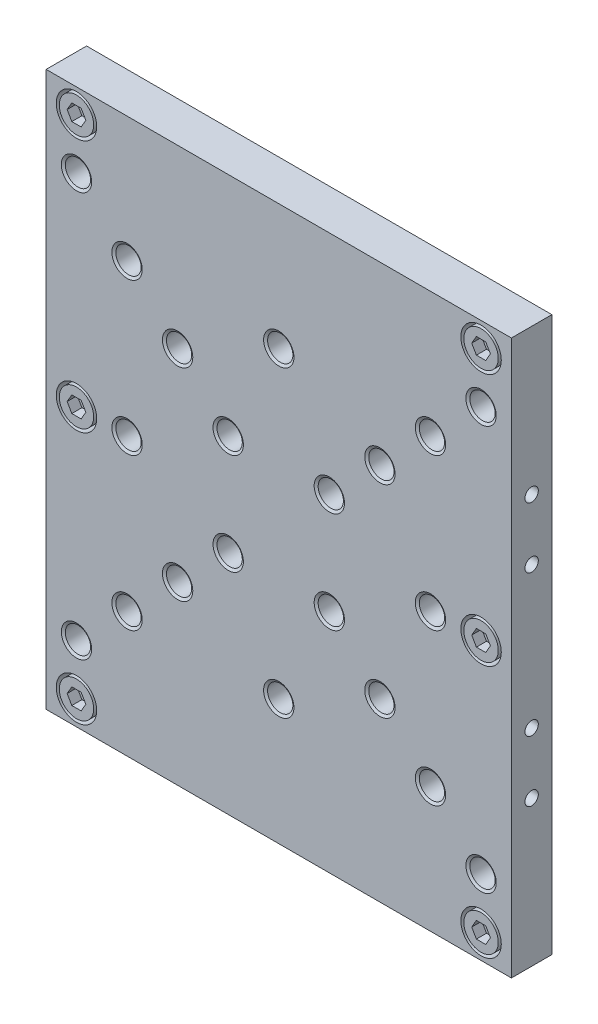
SolidWorks part; units mm, degrees
note: '?' marks a value the reader was unsure of.
material "Aluminum Black Anodize"
ref_plane "Front" through (0, 0, 0) normal (0, 0, 1) x (1, 0, 0)
ref_plane "Top" through (0, 0, 0) normal (0, 1, 0) x (1, 0, 0)
ref_plane "Right" through (0, 0, 0) normal (1, 0, 0) x (0, 0, -1)
ref_axis "Axis1" through (0, 0, -0.5) along (0, 0, 1)?
sketch "Sketch1" plane through (0, 0, 0) normal (0, 0, 1) x (1, 0, 0)
  line L1 (57.5, -68.5) -> (-57.5, -68.5)
  line L2 (57.5, -68.5) -> (57.5, 68.5)
  line L3 (57.5, 68.5) -> (-57.5, 68.5)
  line L4 (-57.5, -68.5) -> (-57.5, 68.5)
  point P4 (57.5, 0)
  point P5 (0, 68.5)
  dimension "D1" = 115
  dimension "D2" = 137
extrude "Extrude1" add sketch "Sketch1" along normal blind 10
hole_wizard "CBORE for M5 SHCS1" positions "Sketch7" profile "Sketch6" counterbore size "M5" standard "ANSI Metric" end condition through all
sketch "Sketch7" plane through (0, 0, 10) normal (0, 0, 1) x (1, 0, 0)
  line L5 (-57.5, 0) -> (57.5, 0) construction
  line L6 (-57.5, 68.5) -> (-57.5, -68.5) construction
  line L7 (57.5, -68.5) -> (57.5, 68.5) construction
  line L8 (0, -68.5) -> (0, 68.5) construction
  line L9 (-57.5, -68.5) -> (57.5, -68.5) construction
  line L10 (57.5, 68.5) -> (-57.5, 68.5) construction
  point P13 (50, 62.5)
  point P15 (50, 0)
  point P48 (-50, 0)
  point P49 (-50, 62.5)
  point P56 (-50, -62.5)
  point P59 (50, -62.5)
  dimension "D1" = 125
  dimension "D9" = 50
sketch "Sketch6" plane through (50, 62.5, 10) normal (1, 0, 0) x (0, -1, 0)
  line L0 (0, 0) -> (0, 10)
  line L1 (0, 10) -> (2.8956, 10)
  line L3 (2.8956, 10) -> (2.8956, 5.5)
  line L4 (2.8956, 5.5) -> (5, 5.5)
  line L5 (5, 5.5) -> (5, 0)
  line L7 (5, 0) -> (0, 0)
  line L11 (0, -6.35) -> (0, 107.95) construction
  dimension "Thru Hole Dia." = 5.7912
  dimension "Thru Hole Depth" = 10
  dimension "C'Bore Dia." = 10
  dimension "C'Bore Depth" = 5.5
hole_wizard "Tapped Hole for M6x1.0 Helicoil1" positions "Sketch3" profile "Sketch2" tap size "M6x1.0" standard "Helicoil® Metric" end condition through all
sketch "Sketch3" plane through (0, 0, 10) normal (0, 0, 1) x (1, 0, 0)
  line L0 (0, 0) -> (-141.3203, 0) construction
  line L1 (0, 0) -> (0, 79.9717) construction
  line L2 (-57.5, -68.5) -> (57.5, -68.5) construction
  point P0 (12.5, 12.5)
  point P1 (-12.5, 12.5)
  point P2 (12.5, -12.5)
  point P7 (-12.5, -12.5)
  point P8 (25, 25)
  point P9 (25, -25)
  point P10 (-25, -25)
  point P11 (-25, 25)
  point P12 (37.5, 37.5)
  point P13 (37.5, -37.5)
  point P14 (-37.5, 37.5)
  point P15 (-37.5, -37.5)
  point P16 (37.5, 0)
  point P21 (-37.5, 0)
  point P22 (0, 37.5)
  point P23 (0, -37.5)
  dimension "D1" = 12.5
  dimension "D2" = 12.5
  dimension "D3" = 25
  dimension "D4" = 25
  dimension "D5" = 37.5
  dimension "D6" = 37.5
cosmetic thread "Hole Thread5" parameters "D1"=7, "D2"=7.422
cosmetic thread "Hole Thread6" parameters "D1"=7, "D2"=7.422
cosmetic thread "Hole Thread7" parameters "D1"=7, "D2"=7.422
cosmetic thread "Hole Thread8" parameters "D1"=7, "D2"=7.422
cosmetic thread "Hole Thread9" parameters "D1"=7, "D2"=7.422
cosmetic thread "Hole Thread10" parameters "D1"=7, "D2"=7.422
cosmetic thread "Hole Thread11" parameters "D1"=7, "D2"=7.422
cosmetic thread "Hole Thread12" parameters "D1"=7, "D2"=7.422
cosmetic thread "Hole Thread13" parameters "D1"=7, "D2"=7.422
cosmetic thread "Hole Thread14" parameters "D1"=7, "D2"=7.422
cosmetic thread "Hole Thread15" parameters "D1"=7, "D2"=7.422
cosmetic thread "Hole Thread16" parameters "D1"=7, "D2"=7.422
cosmetic thread "Hole Thread17" parameters "D1"=7, "D2"=7.422
cosmetic thread "Hole Thread18" parameters "D1"=7, "D2"=7.422
cosmetic thread "Hole Thread19" parameters "D1"=7, "D2"=7.422
cosmetic thread "Hole Thread20" parameters "D1"=7, "D2"=7.422
sketch "Sketch2" plane through (12.5, 12.5, 10) normal (1, 0, 0) x (0, -1, 0)
  line L0 (0, 0) -> (0, 10)
  line L1 (0, 10) -> (3.125, 10)
  line L2 (3.125, 10) -> (3.125, 0.3608)
  line L3 (3.125, 0.3608) -> (3.75, 0)
  line L5 (3.75, 0) -> (0, 0)
  line L6 (-3.125, 0.3608) -> (-3.75, 0) construction
  line L11 (0, -6.35) -> (0, 107.95) construction
  dimension "Thru Tap Drill Dia." = 6.25
  dimension "Thru Tap Drill Depth" = 10
  dimension "Near C'Sink Dia." = 7.5
  dimension "Near C'Sink Angle" = 120
hole_wizard "Tapped Hole for M6x1.0 Helicoil2" positions "Sketch11" profile "Sketch10" tap size "M6x1.0" standard "Helicoil® Metric" end condition through all
sketch "Sketch11" plane through (0, 0, 10) normal (0, 0, 1) x (1, 0, 0)
  line L4 (-50, 50) -> (50, 50) construction
  line L5 (50, 50) -> (50, -50) construction
  line L6 (50, -50) -> (-50, -50) construction
  line L7 (-50, -50) -> (-50, 50) construction
  line L8 (-50, 50) -> (50, -50) construction
  point P0 (-50, 50)
  point P1 (50, 50)
  point P3 (50, -50)
  point P5 (-50, -50)
  dimension "D1" = 100
  dimension "D2" = 100
cosmetic thread "Hole Thread37" parameters "D1"=7, "D2"=7.422
cosmetic thread "Hole Thread38" parameters "D1"=7, "D2"=7.422
cosmetic thread "Hole Thread39" parameters "D1"=7, "D2"=7.422
cosmetic thread "Hole Thread40" parameters "D1"=7, "D2"=7.422
sketch "Sketch10" plane through (-50, 50, 10) normal (1, 0, 0) x (0, -1, 0)
  line L0 (0, 0) -> (0, 10)
  line L1 (0, 10) -> (3.125, 10)
  line L2 (3.125, 10) -> (3.125, 0.3608)
  line L3 (3.125, 0.3608) -> (3.75, 0)
  line L5 (3.75, 0) -> (0, 0)
  line L6 (-3.125, 0.3608) -> (-3.75, 0) construction
  line L11 (0, -6.35) -> (0, 107.95) construction
  dimension "Thru Tap Drill Dia." = 6.25
  dimension "Thru Tap Drill Depth" = 10
  dimension "Near C'Sink Dia." = 7.5
  dimension "Near C'Sink Angle" = 120
hole_wizard "Tapped Hole for 1/4-20 Helicoil1" [suppressed] positions "Sketch9" profile "Sketch8" tap size "1/4-20" standard "Helicoil® Inch"
sketch "Sketch9" [suppressed] plane through (0, 0, 10) normal (0, 0, 1) x (1, 0, 0)
  line L0 (-62.9542, 0) -> (64.4183, 0) construction
  line L1 (0, 59.6195) -> (0, -44.1656) construction
  line L2 (0, 0) -> (69.2893, 69.2893) construction
  point P1 (-12.7, 12.7)
  point P2 (-12.7, -12.7)
  point P3 (12.7, -12.7)
  point P4 (12.7, 12.7)
  point P8 (-25.4, 25.4)
  point P10 (25.4, 25.4)
  point P11 (25.4, -25.4)
  point P12 (-25.4, -25.4)
  point P13 (-38.1, 38.1)
  point P14 (0, 38.1)
  point P15 (38.1, 38.1)
  point P16 (38.1, 0)
  point P17 (38.1, -38.1)
  point P18 (0, -38.1)
  point P19 (-38.1, -38.1)
  point P20 (-38.1, 0)
  point P27 (50.8, 50.8)
  point P30 (-50.8, 50.8)
  point P31 (-50.8, -50.8)
  point P32 (50.8, -50.8)
  dimension "D1" = 12.7
  dimension "D2" = 45
  dimension "D3" = 25.4
  dimension "D4" = 50.8
  dimension "D5" = 38.1
cosmetic thread "Hole Thread21" [suppressed] parameters "D1"=7.62, "D2"=8.095
cosmetic thread "Hole Thread22" [suppressed] parameters "D1"=7.62, "D2"=8.095
cosmetic thread "Hole Thread23" [suppressed] parameters "D1"=7.62, "D2"=8.095
cosmetic thread "Hole Thread24" [suppressed] parameters "D1"=7.62, "D2"=8.095
cosmetic thread "Hole Thread25" [suppressed] parameters "D1"=7.62, "D2"=8.095
cosmetic thread "Hole Thread26" [suppressed] parameters "D1"=7.62, "D2"=8.095
cosmetic thread "Hole Thread27" [suppressed] parameters "D1"=7.62, "D2"=8.095
cosmetic thread "Hole Thread28" [suppressed] parameters "D1"=7.62, "D2"=8.095
cosmetic thread "Hole Thread29" [suppressed] parameters "D1"=7.62, "D2"=8.095
cosmetic thread "Hole Thread30" [suppressed] parameters "D1"=7.62, "D2"=8.095
cosmetic thread "Hole Thread31" [suppressed] parameters "D1"=7.62, "D2"=8.095
cosmetic thread "Hole Thread32" [suppressed] parameters "D1"=7.62, "D2"=8.095
cosmetic thread "Hole Thread33" [suppressed] parameters "D1"=7.62, "D2"=8.095
cosmetic thread "Hole Thread34" [suppressed] parameters "D1"=7.62, "D2"=8.095
cosmetic thread "Hole Thread35" [suppressed] parameters "D1"=7.62, "D2"=8.095
cosmetic thread "Hole Thread36" [suppressed] parameters "D1"=7.62, "D2"=8.095
cosmetic thread "Hole Thread55" [suppressed] parameters "D1"=7.62, "D2"=8.095
cosmetic thread "Hole Thread56" [suppressed] parameters "D1"=7.62, "D2"=8.095
cosmetic thread "Hole Thread57" [suppressed] parameters "D1"=7.62, "D2"=8.095
cosmetic thread "Hole Thread58" [suppressed] parameters "D1"=7.62, "D2"=8.095
sketch "Sketch8" [suppressed] plane through (-12.7, 12.7, 10) normal (1, 0, 0) x (0, -1, 0)
  line L0 (0, 0) -> (0, 10)
  line L1 (0, 10) -> (3.3782, 10)
  line L2 (3.3782, 10) -> (3.3782, 0.4326)
  line L3 (3.3782, 0.4326) -> (4.1275, 0)
  line L5 (4.1275, 0) -> (0, 0)
  line L6 (-3.3782, 0.4326) -> (-4.1275, 0) construction
  line L11 (0, -6.35) -> (0, 107.95) construction
  dimension "Thru Tap Drill Dia." = 6.7564
  dimension "Thru Tap Drill Depth" = 10
  dimension "Near C'Sink Dia." = 8.255
  dimension "Near C'Sink Angle" = 120
hole_wizard "M2.5x0.45 Tapped Hole1" [suppressed] positions "Sketch13" profile "Sketch12" tap size "M2.5x0.45" standard "ANSI Metric"
sketch "Sketch13" [suppressed] plane through (0, -68.5, 0) normal (0, -1, 0) x (1, 0, 0)
  line L4 (0, 0) -> (0, 10) construction
  line L5 (-57.5, 0) -> (57.5, 0) construction
  point P0 (0, 6)
  point P3 (35, 6)
  point P26 (-35, 6)
  dimension "D1" = 6
  dimension "D2" = 35
  dimension "D5" = 35
sketch "Sketch12" [suppressed] plane through (0, -68.5, 6) normal (1, 0, 0) x (0, 0, -1)
  line L0 (0, 0) -> (0, 7.8659)
  line L1 (0, 7.8659) -> (1.025, 7.25)
  line L2 (1.025, 7.25) -> (1.025, 0)
  line L5 (1.025, 0) -> (0, 0)
  line L10 (0, 7.8659) -> (-1.025, 7.25) construction
  line L11 (0, -6.35) -> (0, 107.95) construction
  dimension "Tap Drill Dia." = 2.05
  dimension "Tap Drill Depth" = 7.25
  dimension "Drill Angle" = 118
cosmetic thread "Hole Thread49" [suppressed] parameters "D1"=5, "D2"=2.5
cosmetic thread "Hole Thread50" [suppressed] parameters "D1"=5, "D2"=2.5
cosmetic thread "Hole Thread51" [suppressed] parameters "D1"=5, "D2"=2.5
hole_wizard "M2.5x0.45 Tapped Hole2" [suppressed] positions "Sketch15" profile "Sketch14" tap size "M2.5x0.45" standard "ANSI Metric"
sketch "Sketch15" [suppressed] plane through (0, 68.5, 0) normal (0, 1, 0) x (-1, 0, 0)
  point P5 (-35, 6)
  point P7 (0, 6)
  point P14 (35, 6)
sketch "Sketch14" [suppressed] plane through (35, 68.5, 6) normal (1, 0, 0) x (0, 0, 1)
  line L0 (0, 0) -> (0, 7.8659)
  line L1 (0, 7.8659) -> (1.025, 7.25)
  line L2 (1.025, 7.25) -> (1.025, 0)
  line L5 (1.025, 0) -> (0, 0)
  line L10 (0, 7.8659) -> (-1.025, 7.25) construction
  line L11 (0, -6.35) -> (0, 107.95) construction
  dimension "Tap Drill Dia." = 2.05
  dimension "Tap Drill Depth" = 7.25
  dimension "Drill Angle" = 118
cosmetic thread "Hole Thread52" [suppressed] parameters "D1"=5, "D2"=2.5
cosmetic thread "Hole Thread53" [suppressed] parameters "D1"=5, "D2"=2.5
cosmetic thread "Hole Thread54" [suppressed] parameters "D1"=5, "D2"=2.5
hole_wizard "CBORE for M5 SHCS2" [suppressed] positions "Sketch19" profile "Sketch18" counterbore size "M5" standard "Ansi Metric"
sketch "Sketch19" [suppressed] plane through (0, 0, 0) normal (0, 0, -1) x (-1, 0, 0)
  line L0 (37.5, 12.5) -> (37.5, -12.5) construction
  line L1 (37.5, -12.5) -> (-37.5, -12.5) construction
  line L2 (-37.5, -12.5) -> (-37.5, 12.5) construction
  line L3 (-37.5, 12.5) -> (37.5, 12.5) construction
  line L4 (37.5, 12.5) -> (-37.5, -12.5) construction
  line L5 (12.5, -37.5) -> (-12.5, -37.5) construction
  line L6 (-12.5, -37.5) -> (-12.5, 37.5) construction
  line L7 (-12.5, 37.5) -> (12.5, 37.5) construction
  line L8 (12.5, 37.5) -> (12.5, -37.5) construction
  line L9 (12.5, -37.5) -> (-12.5, 37.5) construction
  point P0 (37.5, -12.5)
  point P1 (-37.5, -12.5)
  point P3 (-37.5, 12.5)
  point P5 (37.5, 12.5)
  point P21 (12.5, -37.5)
  point P23 (-12.5, -37.5)
  point P25 (-12.5, 37.5)
  point P27 (12.5, 37.5)
  dimension "D1" = 25
  dimension "D2" = 50
  dimension "D3" = 25
  dimension "D4" = 61.2903
sketch "Sketch18" [suppressed] plane through (-37.5, -12.5, 0) normal (1, 0, 0) x (0, 1, 0)
  line L0 (0, 0) -> (0, 10)
  line L1 (0, 10) -> (2.8956, 10)
  line L3 (2.8956, 10) -> (2.8956, 5.5)
  line L4 (2.8956, 5.5) -> (5, 5.5)
  line L5 (5, 5.5) -> (5, 0)
  line L7 (5, 0) -> (0, 0)
  line L11 (0, -6.35) -> (0, 107.95) construction
  dimension "Thru Hole Dia." = 5.7912
  dimension "Thru Hole Depth" = 10
  dimension "C'Bore Dia." = 10
  dimension "C'Bore Depth" = 5.5
hole_wizard "Tapped Hole for M6x1.0 Helicoil5" [suppressed] positions "Sketch41" profile "Sketch40" tap size "M6x1.0" standard "Helicoil® Metric"
sketch "Sketch41" [suppressed] plane through (0, 0, 10) normal (0, 0, 1) x (1, 0, 0)
  line L1 (37.5, -37.5) -> (-37.5, -37.5)
  line L2 (37.5, -37.5) -> (37.5, 37.5)
  line L3 (37.5, 37.5) -> (-37.5, 37.5)
  line L4 (-37.5, -37.5) -> (-37.5, 37.5)
  line L5 (37.5, -37.5) -> (-37.5, 37.5) construction
  point P0 (37.5, -37.5)
  point P1 (-37.5, -37.5)
  point P3 (37.5, 37.5)
  point P5 (-37.5, 37.5)
  dimension "D1" = 75
cosmetic thread "Hole Thread81" [suppressed] parameters "D1"=7, "D2"=7.422
cosmetic thread "Hole Thread82" [suppressed] parameters "D1"=7, "D2"=7.422
cosmetic thread "Hole Thread83" [suppressed] parameters "D1"=7, "D2"=7.422
cosmetic thread "Hole Thread84" [suppressed] parameters "D1"=7, "D2"=7.422
sketch "Sketch40" [suppressed] plane through (37.5, -37.5, 10) normal (1, 0, 0) x (0, -1, 0)
  line L0 (0, 0) -> (0, 10)
  line L1 (0, 10) -> (3.124, 10)
  line L2 (3.124, 10) -> (3.124, 0.3614)
  line L3 (3.124, 0.3614) -> (3.75, 0)
  line L5 (3.75, 0) -> (0, 0)
  line L6 (-3.124, 0.3614) -> (-3.75, 0) construction
  line L11 (0, -6.35) -> (0, 107.95) construction
  dimension "Thru Tap Drill Dia." = 6.248
  dimension "Thru Tap Drill Depth" = 10
  dimension "Near C'Sink Dia." = 7.5
  dimension "Near C'Sink Angle" = 120
hole_wizard "CBORE for M5 SHCS3" [suppressed] positions "Sketch39" profile "Sketch38" counterbore size "M5" standard "Ansi Metric"
sketch "Sketch39" [suppressed] plane through (0, 0, 0) normal (0, 0, -1) x (-1, 0, 0)
  line L1 (-12.5, 25) -> (12.5, 25)
  line L2 (-12.5, 25) -> (-12.5, -25)
  line L3 (-12.5, -25) -> (12.5, -25)
  line L4 (12.5, 25) -> (12.5, -25)
  line L5 (-12.5, 25) -> (12.5, -25) construction
  point P0 (-12.5, 25)
  point P1 (12.5, 25)
  point P3 (12.5, -25)
  point P5 (-12.5, -25)
  dimension "D1" = 25
  dimension "D2" = 50
sketch "Sketch38" [suppressed] plane through (12.5, 25, 0) normal (1, 0, 0) x (0, 1, 0)
  line L0 (0, 0) -> (0, 10)
  line L1 (0, 10) -> (2.8956, 10)
  line L3 (2.8956, 10) -> (2.8956, 5.5)
  line L4 (2.8956, 5.5) -> (5, 5.5)
  line L5 (5, 5.5) -> (5, 0)
  line L7 (5, 0) -> (0, 0)
  line L11 (0, -6.35) -> (0, 107.95) construction
  dimension "Thru Hole Dia." = 5.7912
  dimension "Thru Hole Depth" = 10
  dimension "C'Bore Dia." = 10
  dimension "C'Bore Depth" = 5.5
pattern_circular "CirPattern2" [suppressed] count 2 over 90 about axis through (0, 0, -0.5) along (0, 0, 1)
hole_wizard "Tapped Hole for M5x0.8 Helicoil1" [suppressed] positions "Sketch29" profile "Sketch28" tap size "M5x0.8" standard "Helicoil® Metric"
sketch "Sketch29" [suppressed] plane through (0, 0, 10) normal (0, 0, 1) x (1, 0, 0)
  line L0 (-25, 50) -> (25, 52.5) construction
  line L1 (25, 52.5) -> (25, -52.5) construction
  line L2 (25, -52.5) -> (-25, -50) construction
  line L3 (-25, -50) -> (-25, 50) construction
  line L6 (25, 0) -> (0, 0) construction
  line L10 (-25, 0) -> (0, 0) construction
  point P0 (-25, 50)
  point P1 (25, 52.5)
  point P3 (25, -52.5)
  point P5 (-25, -50)
  dimension "D1" = 100
  dimension "D2" = 105
  dimension "D3" = 50
sketch "Sketch28" [suppressed] plane through (-25, 50, 10) normal (1, 0, 0) x (0, -1, 0)
  line L0 (0, 0) -> (0, 10)
  line L1 (0, 10) -> (2.6162, 10)
  line L2 (2.6162, 10) -> (2.6162, 0.2793)
  line L3 (2.6162, 0.2793) -> (3.1, 0)
  line L5 (3.1, 0) -> (0, 0)
  line L6 (-2.6162, 0.2793) -> (-3.1, 0) construction
  line L11 (0, -6.35) -> (0, 107.95) construction
  dimension "Thru Tap Drill Dia." = 5.2324
  dimension "Thru Tap Drill Depth" = 10
  dimension "Near C'Sink Dia." = 6.2
  dimension "Near C'Sink Angle" = 120
cosmetic thread "Hole Thread59" [suppressed] parameters "D1"=8.87, "D2"=6.145
cosmetic thread "Hole Thread60" [suppressed] parameters "D1"=8.87, "D2"=6.145
cosmetic thread "Hole Thread61" [suppressed] parameters "D1"=8.87, "D2"=6.145
cosmetic thread "Hole Thread62" [suppressed] parameters "D1"=8.87, "D2"=6.145
pattern_circular "CirPattern1" [suppressed] count 2 over 90 about axis through (0, 0, -0.5) along (0, 0, 1)
hole_wizard "Tapped Hole for M5x0.8 Helicoil2" [suppressed] positions "Sketch31" profile "Sketch33" tap size "M5x0.8" standard "Helicoil® Metric"
sketch "Sketch31" [suppressed] plane through (0, 0, 10) normal (0, 0, 1) x (1, 0, 0)
  line L12 (-25, 62.5) -> (25, 62.5) construction
  line L16 (25, -62.5) -> (-25, -62.5) construction
  line L18 (-25, 50) -> (-25, 62.5) construction
  line L20 (25, 52.5) -> (25, 62.5) construction
  line L22 (25, -62.5) -> (25, -52.5) construction
  line L24 (-25, -62.5) -> (-25, -50) construction
  point P37 (-25, 62.5)
  point P39 (25, 62.5)
  point P41 (-25, -62.5)
  point P43 (25, -62.5)
  dimension "D4" = 125
sketch "Sketch33" [suppressed] plane through (-25, 62.5, 10) normal (1, 0, 0) x (0, -1, 0)
  line L0 (0, 0) -> (0, 10)
  line L1 (0, 10) -> (2.6162, 10)
  line L2 (2.6162, 10) -> (2.6162, 0.2793)
  line L3 (2.6162, 0.2793) -> (3.1, 0)
  line L5 (3.1, 0) -> (0, 0)
  line L6 (-2.6162, 0.2793) -> (-3.1, 0) construction
  line L11 (0, -6.35) -> (0, 107.95) construction
  dimension "Thru Tap Drill Dia." = 5.2324
  dimension "Thru Tap Drill Depth" = 10
  dimension "Near C'Sink Dia." = 6.2
  dimension "Near C'Sink Angle" = 120
cosmetic thread "Hole Thread67" [suppressed] parameters "D1"=8.87, "D2"=6.145
cosmetic thread "Hole Thread68" [suppressed] parameters "D1"=8.87, "D2"=6.145
cosmetic thread "Hole Thread75" [suppressed] parameters "D1"=8.87, "D2"=6.145
cosmetic thread "Hole Thread76" [suppressed] parameters "D1"=8.87, "D2"=6.145
hole_wizard "M4x0.7 Tapped Hole1" positions "Sketch43" profile "Sketch42" tap size "M4x0.7" standard "ANSI Metric"
sketch "Sketch43" plane through (-57.5, 0, 0) normal (-1, 0, 0) x (0, 0, 1)
  line L5 (10, 68.5) -> (10, -68.5) construction
  line L13 (5, 25) -> (10, 25) construction
  line L14 (5, 17.5) -> (5, 32.5) construction
  line L16 (37.0877, 0) -> (-12.7564, 0) construction
  line L20 (5, -32.5) -> (5, -17.5) construction
  line L21 (5, -25) -> (20.6745, -25) construction
  line L22 (5, -17.5) -> (5, 0) construction
  line L23 (5, 0) -> (5, 17.5) construction
  point P36 (5, 17.5)
  point P37 (5, 32.5)
  point P48 (5, -32.5)
  point P54 (5, -17.5)
  dimension "D2" = 5
  dimension "D4" = 15
  dimension "D5" = 25
sketch "Sketch42" plane through (-57.5, 17.5, 5) normal (0, 1, 0) x (0, 0, 1)
  line L0 (0, 0) -> (0, 11.0914)
  line L1 (0, 11.0914) -> (1.65, 10.1)
  line L2 (1.65, 10.1) -> (1.65, 0)
  line L5 (1.65, 0) -> (0, 0)
  line L10 (0, 11.0914) -> (-1.65, 10.1) construction
  line L11 (0, -6.35) -> (0, 107.95) construction
  dimension "Tap Drill Dia." = 3.3
  dimension "Tap Drill Depth" = 10.1
  dimension "Drill Angle" = 118
cosmetic thread "Hole Thread85" parameters "D1"=8, "D2"=4
cosmetic thread "Hole Thread86" parameters "D1"=8, "D2"=4
cosmetic thread "Hole Thread108" parameters "D1"=8, "D2"=4
cosmetic thread "Hole Thread109" parameters "D1"=8, "D2"=4
hole_wizard "M4x0.7 Tapped Hole2" positions "Sketch46" profile "Sketch44" tap size "M4x0.7" standard "ANSI Metric"
sketch "Sketch46" plane through (57.5, 0, 0) normal (1, 0, 0) x (0, 0, -1)
  line L0 (-5, 17.5) -> (-5, 32.5) construction
  line L5 (-5, 25) -> (-10, 25) construction
  line L6 (-10, -68.5) -> (-10, 68.5) construction
  line L13 (-36.1819, 0) -> (23.1872, 0) construction
  line L17 (-5, -32.5) -> (-5, -17.5) construction
  line L18 (-5, -25) -> (-25.8987, -25) construction
  line L19 (-5, -17.5) -> (-5, 0) construction
  line L20 (-5, 0) -> (-5, 17.5) construction
  point P8 (-5, 32.5)
  point P10 (-5, 17.5)
  point P42 (-5, -32.5)
  point P46 (-5, -17.5)
  dimension "D1" = 25
  dimension "D3" = 5
  dimension "D4" = 15
sketch "Sketch44" plane through (57.5, 32.5, 5) normal (0, 1, 0) x (0, 0, -1)
  line L0 (0, 0) -> (0, 11.0914)
  line L1 (0, 11.0914) -> (1.65, 10.1)
  line L2 (1.65, 10.1) -> (1.65, 0)
  line L5 (1.65, 0) -> (0, 0)
  line L10 (0, 11.0914) -> (-1.65, 10.1) construction
  line L11 (0, -6.35) -> (0, 107.95) construction
  dimension "Tap Drill Dia." = 3.3
  dimension "Tap Drill Depth" = 10.1
  dimension "Drill Angle" = 118
cosmetic thread "Hole Thread91" parameters "D1"=8, "D2"=4
cosmetic thread "Hole Thread92" parameters "D1"=8, "D2"=4
cosmetic thread "Hole Thread110" parameters "D1"=8, "D2"=4
cosmetic thread "Hole Thread111" parameters "D1"=8, "D2"=4
hole_wizard "1/4-20 Tapped Hole1" positions "Sketch17" profile "Sketch16" tap size "1/4-20" standard "ANSI Inch"
sketch "Sketch17" plane through (0, 0, 0) normal (0, 0, -1) x (-1, 0, 0)
  line L0 (0, -50) -> (0, 50) construction
  point P1 (0, 50)
  dimension "D1" = 50
sketch "Sketch16" plane through (0, 50, 0) normal (1, 0, 0) x (0, 1, 0)
  line L0 (0, 0) -> (0, 9.1691)
  line L1 (0, 9.1691) -> (2.5781, 7.62)
  line L2 (2.5781, 7.62) -> (2.5781, 0)
  line L5 (2.5781, 0) -> (0, 0)
  line L10 (0, 9.1691) -> (-2.5781, 7.62) construction
  line L11 (0, -6.35) -> (0, 107.95) construction
  dimension "Tap Drill Dia." = 5.1562
  dimension "Tap Drill Depth" = 7.62
  dimension "Drill Angle" = 118
cosmetic thread "Hole Thread107" parameters "D1"=6.35, "D2"=6.35
sketch "Sketch47" plane through (0, 0, 0) normal (0, 0, -1) x (-1, 0, 0)
  line L0 (57.5, 38.88) -> (51, 38.88)
  line L1 (57.5, 68.5) -> (57.5, -68.5) construction
  line L2 (47.825, 35.705) -> (47.825, 9.795)
  line L3 (51, 6.62) -> (57.5, 6.62)
  line L4 (57.5, 6.62) -> (57.5, 38.88)
  line L5 (57.5, -68.5) -> (-57.5, -68.5) construction
  line L6 (-57.5, 68.5) -> (57.5, 68.5) construction
  line L7 (57.5, -16) -> (46.68, -16)
  line L8 (57.5, -16) -> (57.5, -27)
  line L9 (57.5, -27) -> (46.68, -27)
  line L10 (43.5, -19.18) -> (43.5, -23.82)
  arc A0 (51, 38.88) -> (47.825, 35.705) centre (51, 35.705) ccw
  arc A1 (47.825, 9.795) -> (51, 6.62) centre (51, 9.795) ccw
  arc A2 (46.68, -27) -> (43.5, -23.82) centre (46.68, -23.82) cw
  arc A3 (46.68, -16) -> (43.5, -19.18) centre (46.68, -19.18) ccw
  dimension "D4" = 3.175
  dimension "D7" = 3.18
  dimension "D1" = 32.26
  dimension "D2" = 61.88
  dimension "D3" = 6.5
  dimension "D5" = 41.5
  dimension "D6" = 52.5
  dimension "D8" = 14
extrude "Cut-Extrude1" cut sketch "Sketch47" against normal blind 1
ref_axis "Axis2" [suppressed] through (-35, -61.25, 6) along (0, -1, 0)?
ref_axis "Axis3" [suppressed] through (35, -61.25, 6) along (0, -1, 0)?
ref_plane "Plane1" [suppressed] through (0, 0, 6) normal (0, 0, -1) x (-1, 0, 0)
sketch "Sketch48" plane through (0, 0, 10) normal (0, 0, 1) x (1, 0, 0)
  circle A0 centre (50, -62.5) radius 4.25
  circle A1 centre (-50, -62.5) radius 4.25
  circle A2 centre (-50, 0) radius 4.25
  circle A3 centre (50, 0) radius 4.25
  circle A4 centre (50, 62.5) radius 4.25
  circle A5 centre (-50, 62.5) radius 4.25
  dimension "D1" = 8.5
extrude "Boss-Extrude1" add sketch "Sketch48" against normal blind 5 separate body
sketch "Sketch49" plane through (0, 0, 10) normal (0, 0, 1) x (1, 0, 0)
  line L0 (51.1547, -64.5) -> (48.8453, -64.5)
  line L1 (48.8453, -64.5) -> (47.6906, -62.5)
  line L2 (47.6906, -62.5) -> (48.8453, -60.5)
  line L3 (51.1547, -60.5) -> (48.8453, -60.5)
  line L4 (51.1547, -60.5) -> (52.3094, -62.5)
  line L5 (52.3094, -62.5) -> (51.1547, -64.5)
  line L6 (-48.8453, -64.5) -> (-51.1547, -64.5)
  line L7 (-51.1547, -64.5) -> (-52.3094, -62.5)
  line L8 (-52.3094, -62.5) -> (-51.1547, -60.5)
  line L9 (-48.8453, -60.5) -> (-51.1547, -60.5)
  line L10 (-48.8453, -60.5) -> (-47.6906, -62.5)
  line L11 (-47.6906, -62.5) -> (-48.8453, -64.5)
  line L12 (-48.8453, -2) -> (-51.1547, -2)
  line L13 (-51.1547, -2) -> (-52.3094, 0)
  line L14 (-52.3094, 0) -> (-51.1547, 2)
  line L15 (-48.8453, 2) -> (-51.1547, 2)
  line L16 (-48.8453, 2) -> (-47.6906, 0)
  line L17 (-47.6906, 0) -> (-48.8453, -2)
  line L18 (-48.8453, 60.5) -> (-51.1547, 60.5)
  line L19 (-51.1547, 60.5) -> (-52.3094, 62.5)
  line L20 (-52.3094, 62.5) -> (-51.1547, 64.5)
  line L21 (-48.8453, 64.5) -> (-51.1547, 64.5)
  line L22 (-48.8453, 64.5) -> (-47.6906, 62.5)
  line L23 (-47.6906, 62.5) -> (-48.8453, 60.5)
  line L24 (51.1547, -2) -> (48.8453, -2)
  line L25 (48.8453, -2) -> (47.6906, 0)
  line L26 (47.6906, 0) -> (48.8453, 2)
  line L27 (51.1547, 2) -> (48.8453, 2)
  line L28 (51.1547, 2) -> (52.3094, 0)
  line L29 (52.3094, 0) -> (51.1547, -2)
  line L30 (51.1547, 60.5) -> (48.8453, 60.5)
  line L31 (48.8453, 60.5) -> (47.6906, 62.5)
  line L32 (47.6906, 62.5) -> (48.8453, 64.5)
  line L33 (51.1547, 64.5) -> (48.8453, 64.5)
  line L34 (51.1547, 64.5) -> (52.3094, 62.5)
  line L35 (52.3094, 62.5) -> (51.1547, 60.5)
  circle A0 centre (-50, -62.5) radius 2 construction
  circle A1 centre (50, -62.5) radius 2 construction
  circle A2 centre (-50, 0) radius 2 construction
  circle A3 centre (-50, 62.5) radius 2 construction
  circle A4 centre (50, 0) radius 2 construction
  circle A5 centre (50, 62.5) radius 2 construction
  point P7 (50, -64.5)
  point P20 (-50, -64.5)
  point P29 (-50, -2)
  point P38 (-50, 60.5)
  point P47 (50, -2)
  point P56 (50, 60.5)
  dimension "D1" = 4
  dimension "D2" = 2
  dimension "D3" = 3
extrude "Cut-Extrude2" cut sketch "Sketch49" against normal blind 2.5
